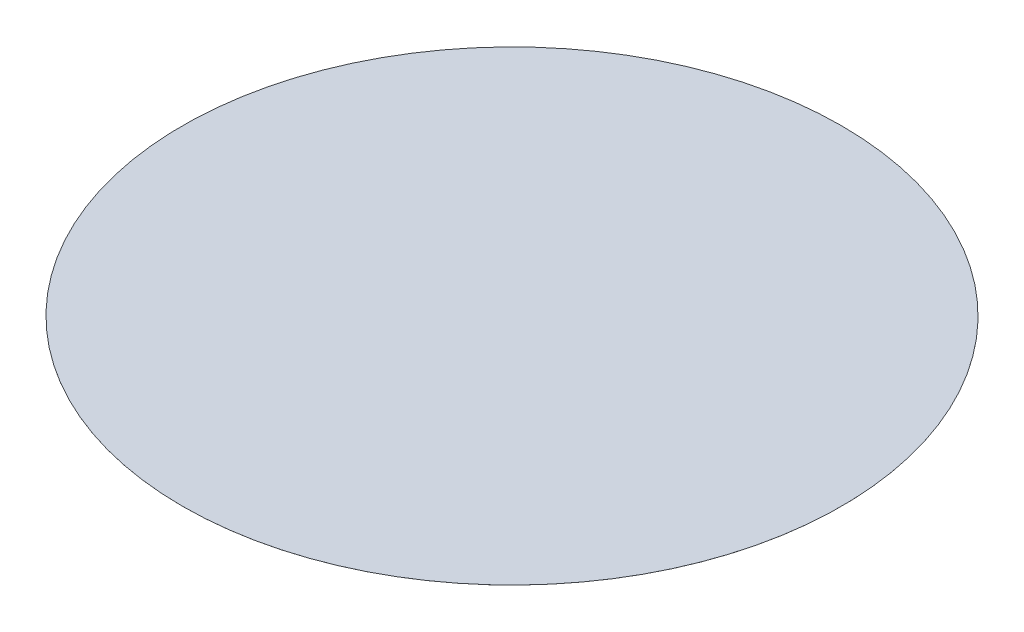
SolidWorks part; units mm, degrees
ref_plane "Front Plane" through (0, 0, 0) normal (0, 0, 1) x (1, 0, 0)
ref_plane "Top Plane" through (0, 0, 0) normal (0, 1, 0) x (1, 0, 0)
ref_plane "Right Plane" through (0, 0, 0) normal (1, 0, 0) x (0, 0, -1)
ref_axis "Axis X" through (0, 0, 0) along (1, 0, 0)
ref_axis "Axis Y" through (0, 0, 0) along (0, 1, 0)
ref_axis "Axis Z" through (0, 0, 0) along (0, 0, 1)
sketch "Sketch1" plane through (0, 0, 0) normal (0, 1, 0) x (1, 0, 0)
  circle A0 centre (0, 0) radius 1418
  dimension "D1" = 2836
extrude "CRX-10iAL_MaxReachReference" add sketch "Sketch1" along normal blind 0.1
